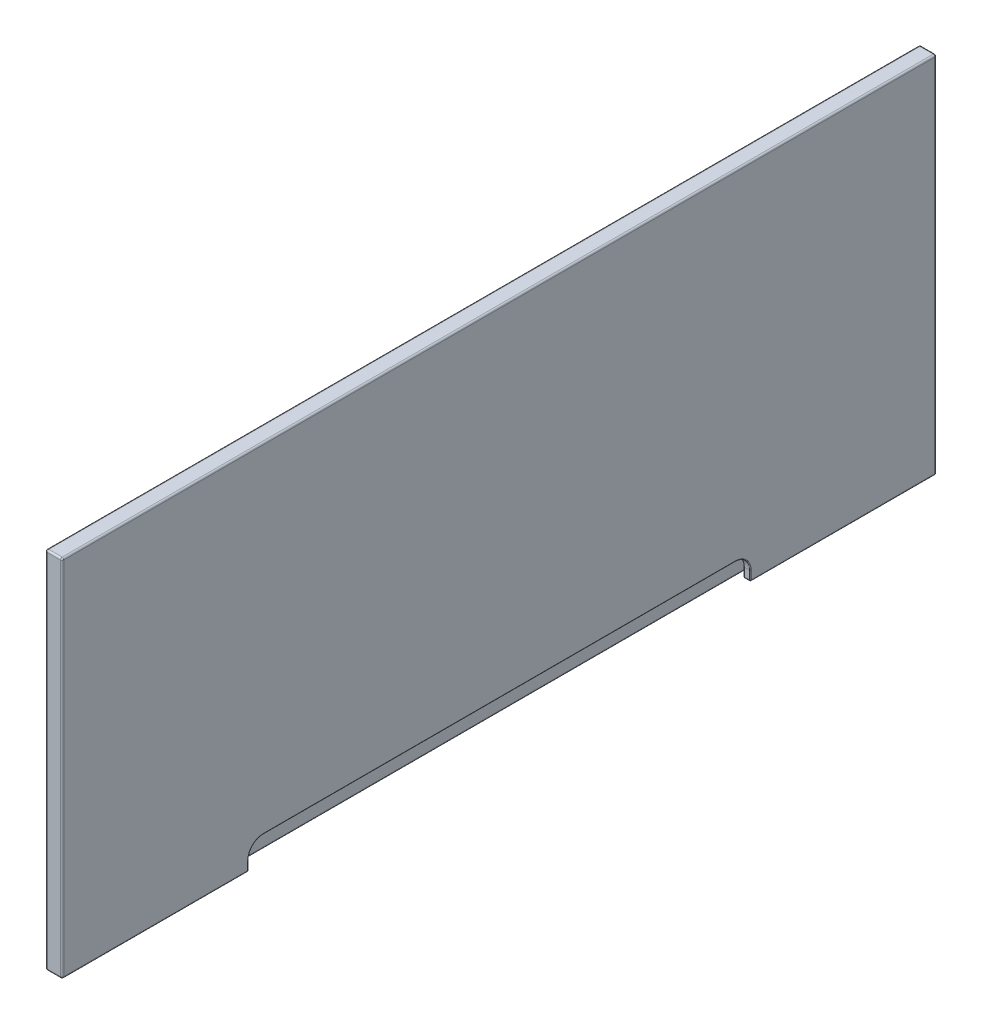
SolidWorks part; units mm, degrees
ref_plane "Front Plane" through (0, 0, 0) normal (0, 0, 1) x (1, 0, 0)
ref_plane "Top Plane" through (0, 0, 0) normal (0, 1, 0) x (1, 0, 0)
ref_plane "Right Plane" through (0, 0, 0) normal (1, 0, 0) x (0, 0, -1)
sketch "Sketch1" plane through (0, 0, 0) normal (1, 0, 0) x (0, 0, -1)
  line L1 (522.64, -217.675) -> (-522.64, -217.675)
  line L2 (522.64, -217.675) -> (522.64, 217.675)
  line L3 (522.64, 217.675) -> (-522.64, 217.675)
  line L4 (-522.64, -217.675) -> (-522.64, 217.675)
  line L5 (522.64, -217.675) -> (-522.64, 217.675) construction
  line L6 (522.64, 217.675) -> (-522.64, -217.675) construction
  point P0 (0, 0)
  dimension "D1" = 1045.28
  dimension "D2" = 435.35
extrude "Boss-Extrude1" add sketch "Sketch1" against normal blind 20
sketch "Sketch3" plane through (0, 0, 0) normal (1, 0, 0) x (0, 0, -1)
  line L0 (-522.64, -217.675) -> (522.64, -217.675) construction
  line L1 (-300, -217.675) -> (300, -217.675)
  line L2 (-300, -217.675) -> (-300, -205.675)
  line L3 (-282, -187.675) -> (282, -187.675)
  line L4 (300, -217.675) -> (300, -205.675)
  arc A0 (282, -187.675) -> (300, -205.675) centre (282, -205.675) cw
  arc A1 (-300, -205.675) -> (-282, -187.675) centre (-282, -205.675) cw
  point P4 (0, -217.675)
  point P10 (300, -187.675)
  point P13 (-300, -187.675)
  dimension "D3" = 18
  dimension "D1" = 30
  dimension "D2" = 600
extrude "Cut-Extrude2" cut sketch "Sketch3" against normal blind 15
sketch "Sketch4" plane through (-15, 0, 0) normal (1, 0, 0) x (0, 0, -1)
  line L0 (-300, -217.675) -> (300, -217.675) construction
  line L1 (-310, -217.675) -> (310, -217.675)
  line L2 (-310, -217.675) -> (-310, -200.675)
  line L3 (-287, -177.675) -> (287, -177.675)
  line L4 (310, -217.675) -> (310, -200.675)
  arc A0 (287, -177.675) -> (310, -200.675) centre (287, -200.675) cw
  arc A1 (-310, -200.675) -> (-287, -177.675) centre (-287, -200.675) cw
  point P6 (0, -177.675)
  point P10 (310, -177.675)
  point P13 (-310, -177.675)
  dimension "D3" = 23
  dimension "D1" = 620
  dimension "D2" = 40
extrude "Cut-Extrude3" cut sketch "Sketch4" along normal blind 7
fillet "Fillet1" radius 1 20 edges at (-8, -209.175, -310) (-8, -184.4115, -303.2635) (-8, -177.675, 0) (-8, -209.175, 310) (0, -211.675, -300) (0, -192.9471, -294.7279) (0, -211.675, 300) (0, -192.9471, 294.7279) (-8, -211.675, -300) (-8, -192.9471, -294.7279) (-8, -211.675, 300) (-8, -192.9471, 294.7279) (-15, -209.175, -310) (-15, -184.4115, -303.2635) (-15, -209.175, 310) (-15, -184.4115, 303.2635) (-8, -184.4115, 303.2635) (0, -187.675, 0) (-8, -187.675, 0) (-15, -177.675, 0)
fillet "Fillet2" radius 2 28 edges at (-10, -217.675, -522.64) (-0.2929, -217.675, 300.2929) (-4, -217.675, 300) (-7.7071, -217.675, 300.2929) (-8, -217.675, 305) (-8.2929, -217.675, 309.7071) (-11.5, -217.675, 310) (-14.7071, -217.675, 309.7071) (-15, -217.675, 0) (-14.7071, -217.675, -309.7071) (-11.5, -217.675, -310) (-8.2929, -217.675, -309.7071) (-8, -217.675, -305) (-7.7071, -217.675, -300.2929) (-4, -217.675, -300) (-0.2929, -217.675, -300.2929) (-10, -217.675, 522.64) (-20, -217.675, 0) (-20, 0, -522.64) (-20, 0, 522.64) (-10, 217.675, 522.64) (-20, 217.675, 0) (-10, 217.675, -522.64) (0, -217.675, 411.82) (0, 0, 522.64) (0, 217.675, 0) (0, 0, -522.64) (0, -217.675, -411.82)
